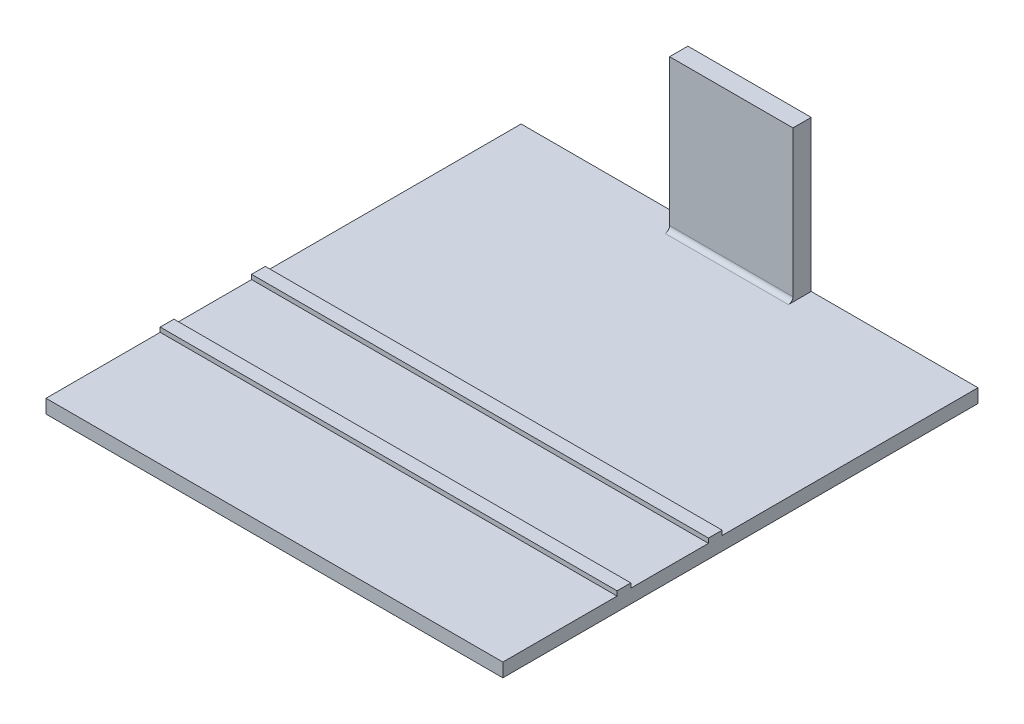
SolidWorks part; units mm, degrees
ref_plane "Piano frontale" through (0, 0, 0) normal (0, 0, 1) x (1, 0, 0)
ref_plane "Piano superiore" through (0, 0, 0) normal (0, 1, 0) x (1, 0, 0)
ref_plane "Piano destro" through (0, 0, 0) normal (1, 0, 0) x (0, 0, -1)
sketch "Schizzo1" plane through (0, 0, 0) normal (0, 0, 1) x (1, 0, 0)
  line L1 (0, 0) -> (27, 0)
  line L2 (0, 0) -> (0, -36)
  line L3 (0, -36) -> (27, -36)
  line L4 (27, 0) -> (27, -36)
  dimension "D1" = 27
  dimension "D2" = 36
extrude "Estrusione-Estrusione1" add sketch "Schizzo1" along normal blind 4
sketch "Schizzo3" plane through (0, 0, 4) normal (0, 0, 1) x (1, 0, 0)
  line L0 (27, -36) -> (27, 0) construction
  line L1 (0, -36) -> (27, -36)
  line L2 (0, -36) -> (0, -33)
  line L3 (0, -33) -> (27, -33)
  line L4 (27, -36) -> (27, -33)
  dimension "D1" = 3
extrude "Estrusione-Estrusione2" add sketch "Schizzo3" along normal blind 100
fillet "Raccordo1" radius 1 1 edges at (13.5, -33, 4)
sketch "Schizzo5" plane through (27, 0, 0) normal (1, 0, 0) x (0, 0, -1)
  line L0 (0, -36) -> (0, 0) construction
  line L1 (-104, -36) -> (0, -36)
  line L2 (-104, -36) -> (-104, -33)
  line L3 (-104, -33) -> (0, -33)
  line L4 (0, -36) -> (0, -33)
  line L9 (-104, -33) -> (-5, -33) construction
extrude "Estrusione-Estrusione3" add sketch "Schizzo5" along normal blind 36.5 and the other way blind 63.5
sketch "Schizzo6" plane through (-36.5, 0, 0) normal (-1, 0, 0) x (0, 0, 1)
  line L0 (56, -33) -> (56, -32.5)
  line L1 (0, -33) -> (104, -33) construction
  line L3 (56, -32.5) -> (56, -32)
  line L4 (56, -32) -> (59, -32)
  line L5 (59, -32) -> (59, -32.5)
  line L6 (76, -33) -> (79, -33)
  line L7 (59, -32.5) -> (59, -33)
  line L8 (76, -33) -> (76, -32)
  line L9 (76, -32) -> (79, -32)
  line L10 (79, -33) -> (79, -32)
  line M11 (104, -33) -> (0, -33)
  dimension "D1" = 1
  dimension "D2" = 3
  dimension "D3" = 3
  dimension "D4" = 1
  dimension "D5" = 17
  dimension "D6" = 25
extrude "Estrusione-Estrusione4" add sketch "Schizzo6" against normal blind 100 contours L7 L5 L4 L3 L0 M11 | L10 L9 L8 M11 region at (-36.5, -32.5, 77.5) region at (-36.5, -32.5, 57.5)
